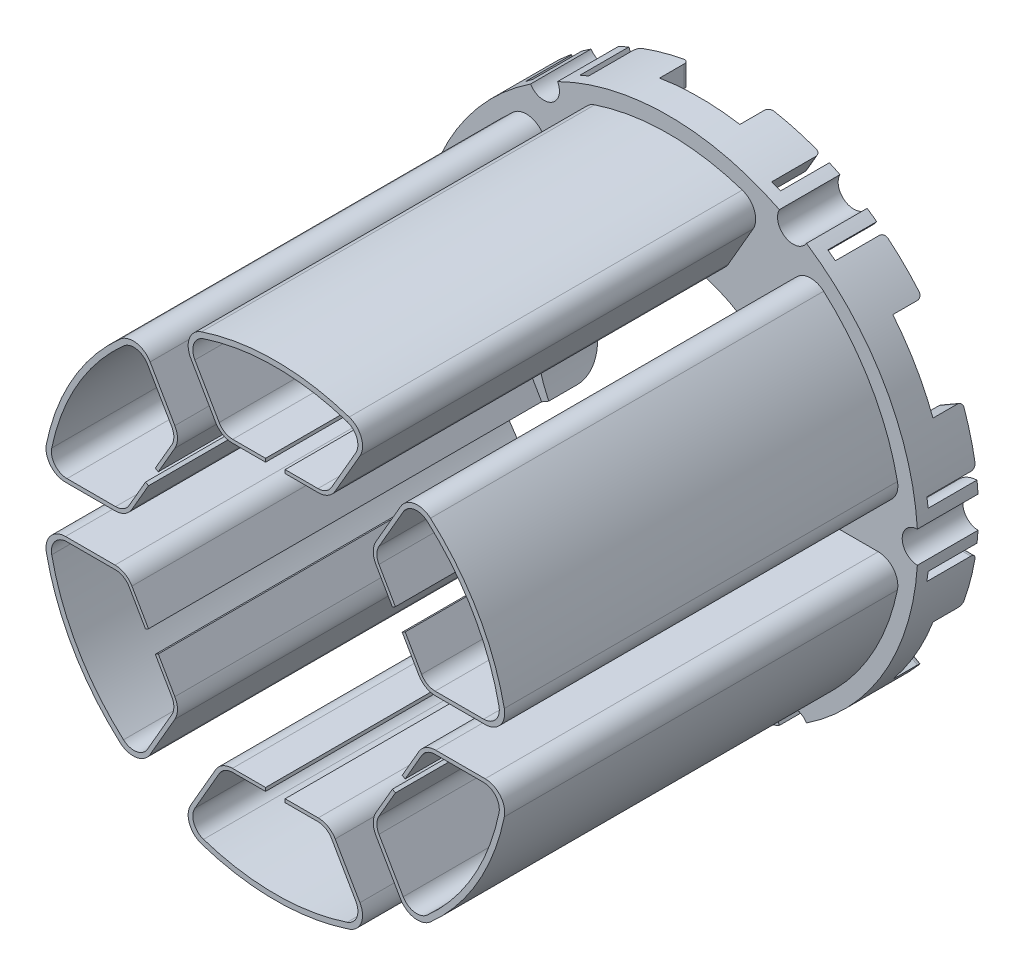
SolidWorks part; units mm, degrees
ref_plane "Ön Düzlem" through (0, 0, 0) normal (0, 0, 1) x (1, 0, 0)
ref_plane "Üst Düzlem" through (0, 0, 0) normal (0, 1, 0) x (1, 0, 0)
ref_plane "Sağ Düzlem" through (0, 0, 0) normal (1, 0, 0) x (0, 0, -1)
sketch "Çizim1" plane through (0, 0, 0) normal (0, 0, 1) x (1, 0, 0)
  line L0 (-5.5426, 14.4) -> (5.5426, 14.4)
  line L1 (9.6995, 12) -> (15.242, 2.4)
  line L2 (15.242, -2.4) -> (9.6995, -12)
  line L3 (5.5426, -14.4) -> (-5.5426, -14.4)
  line L4 (-9.6995, -12) -> (-15.242, -2.4)
  line L5 (-15.242, 2.4) -> (-9.6995, 12)
  line L7 (15.242, 2.4) -> (23.7792, 2.4)
  line L9 (9.6995, 12) -> (13.9681, 19.3934)
  line L10 (9.6995, -12) -> (13.9681, -19.3934)
  line L12 (-5.5426, 14.4) -> (-9.8111, 21.7934)
  line L13 (5.5426, 14.4) -> (9.8111, 21.7934)
  line L14 (15.242, -2.4) -> (23.7792, -2.4)
  line L15 (-5.5426, -14.4) -> (-9.8111, -21.7934)
  line L17 (5.5426, -14.4) -> (9.8111, -21.7934)
  line L18 (-15.242, -2.4) -> (-23.7792, -2.4)
  line L20 (-9.6995, -12) -> (-13.9681, -19.3934)
  line L21 (-9.6995, 12) -> (-13.9681, 19.3934)
  line L23 (-15.242, 2.4) -> (-23.7792, 2.4)
  arc A0 (-23.7792, -2.4) -> (-13.9681, -19.3934) centre (0, 0) ccw
  arc A1 (-13.9681, 19.3934) -> (-23.7792, 2.4) centre (0, 0) ccw
  arc A2 (9.8111, 21.7934) -> (-9.8111, 21.7934) centre (0, 0) ccw
  arc A3 (23.7792, 2.4) -> (13.9681, 19.3934) centre (0, 0) ccw
  arc A4 (13.9681, -19.3934) -> (23.7792, -2.4) centre (0, 0) ccw
  arc A5 (-9.8111, -21.7934) -> (9.8111, -21.7934) centre (0, 0) ccw
  point P6 (0, 14.4)
  point P18 (0, 0)
  point P32 (0, 0)
  point P43 (0, 0)
  dimension "D1" = 47.8
  dimension "D2" = 6
  dimension "D3" = 4.8
  dimension "D4" = 28.8
  dimension "D5" = 120
  dimension "D7" = 120
  dimension "D6" = 6
extrude "Yükseklik-Ekstrüzyon1" add sketch "Çizim1" along normal blind 40.2
sketch "Çizim2" plane through (0, 0, 0) normal (0, 0, -1) x (-1, 0, 0)
  circle A0 centre (0, 0) radius 25.5
  circle A1 centre (0, 0) radius 13.6
  dimension "D1" = 51
  dimension "D2" = 27.2
extrude "Yükseklik-Ekstrüzyon2" add sketch "Çizim2" along normal blind 1.2
sketch "Çizim3" plane through (0, 0, 40.2) normal (0, 0, 1) x (1, 0, 0)
  line L36 (-10.5944, 12.75) -> (-13.075, 17.0466)
  line L37 (-21.3003, 2.8) -> (-16.339, 2.8)
  line L38 (-14.9534, 3.6) -> (-10.5944, 11.15)
  line L39 (4.359, -14.75) -> (-4.359, -14.75)
  line L40 (-5.7446, -15.55) -> (-8.2253, -19.8466)
  line L41 (8.2253, -19.8466) -> (5.7446, -15.55)
  line L42 (-16.339, -2.8) -> (-21.3003, -2.8)
  line L43 (-13.075, -17.0466) -> (-10.5944, -12.75)
  line L44 (-10.5944, -11.15) -> (-14.9534, -3.6)
  line L45 (21.3003, -2.8) -> (16.339, -2.8)
  line L46 (14.9534, -3.6) -> (10.5944, -11.15)
  line L47 (10.5944, -12.75) -> (13.075, -17.0466)
  line L48 (13.075, 17.0466) -> (10.5944, 12.75)
  line L49 (10.5944, 11.15) -> (14.9534, 3.6)
  line L50 (16.339, 2.8) -> (21.3003, 2.8)
  line L51 (5.7446, 15.55) -> (8.2253, 19.8466)
  line L52 (-8.2253, 19.8466) -> (-5.7446, 15.55)
  line L53 (-4.359, 14.75) -> (4.359, 14.75)
  arc A60 (-13.075, 17.0466) -> (-15.5244, 17.4417) centre (-14.4607, 16.2466) ccw
  arc A61 (-15.5244, 17.4417) -> (-22.8672, 4.7237) centre (0, 0) ccw
  arc A62 (-22.8672, 4.7237) -> (-21.3003, 2.8) centre (-21.3003, 4.4) ccw
  arc A63 (-16.339, 2.8) -> (-14.9534, 3.6) centre (-16.339, 4.4) ccw
  arc A64 (-10.5944, 11.15) -> (-10.5944, 12.75) centre (-11.98, 11.95) ccw
  arc A65 (-4.359, -14.75) -> (-5.7446, -15.55) centre (-4.359, -16.35) ccw
  arc A66 (-8.2253, -19.8466) -> (-7.3428, -22.1654) centre (-6.8396, -20.6466) ccw
  arc A67 (-7.3428, -22.1654) -> (7.3428, -22.1654) centre (0, 0) ccw
  arc A68 (7.3428, -22.1654) -> (8.2253, -19.8466) centre (6.8396, -20.6466) ccw
  arc A69 (5.7446, -15.55) -> (4.359, -14.75) centre (4.359, -16.35) ccw
  arc A70 (-21.3003, -2.8) -> (-22.8672, -4.7237) centre (-21.3003, -4.4) ccw
  arc A71 (-22.8672, -4.7237) -> (-15.5244, -17.4417) centre (0, 0) ccw
  arc A72 (-15.5244, -17.4417) -> (-13.075, -17.0466) centre (-14.4607, -16.2466) ccw
  arc A73 (-10.5944, -12.75) -> (-10.5944, -11.15) centre (-11.98, -11.95) ccw
  arc A74 (-14.9534, -3.6) -> (-16.339, -2.8) centre (-16.339, -4.4) ccw
  arc A75 (16.339, -2.8) -> (14.9534, -3.6) centre (16.339, -4.4) ccw
  arc A76 (10.5944, -11.15) -> (10.5944, -12.75) centre (11.98, -11.95) ccw
  arc A77 (13.075, -17.0466) -> (15.5244, -17.4417) centre (14.4607, -16.2466) ccw
  arc A78 (15.5244, -17.4417) -> (22.8672, -4.7237) centre (0, 0) ccw
  arc A79 (22.8672, -4.7237) -> (21.3003, -2.8) centre (21.3003, -4.4) ccw
  arc A80 (22.8672, 4.7237) -> (15.5244, 17.4417) centre (0, 0) ccw
  arc A81 (15.5244, 17.4417) -> (13.075, 17.0466) centre (14.4607, 16.2466) ccw
  arc A82 (10.5944, 12.75) -> (10.5944, 11.15) centre (11.98, 11.95) ccw
  arc A83 (14.9534, 3.6) -> (16.339, 2.8) centre (16.339, 4.4) ccw
  arc A84 (21.3003, 2.8) -> (22.8672, 4.7237) centre (21.3003, 4.4) ccw
  arc A85 (8.2253, 19.8466) -> (7.3428, 22.1654) centre (6.8396, 20.6466) ccw
  arc A86 (7.3428, 22.1654) -> (-7.3428, 22.1654) centre (0, 0) ccw
  arc A87 (-7.3428, 22.1654) -> (-8.2253, 19.8466) centre (-6.8396, 20.6466) ccw
  arc A88 (-5.7446, 15.55) -> (-4.359, 14.75) centre (-4.359, 16.35) ccw
  arc A89 (4.359, 14.75) -> (5.7446, 15.55) centre (4.359, 16.35) ccw
extrude "Kes-Ekstrüzyon1" cut sketch "Çizim3" against normal up to surface (41.4 mm away) up to face at (-25.5, 0, -1.2)
sketch "Çizim4" plane through (0, 0, 40.2) normal (0, 0, 1) x (1, 0, 0)
  line L0 (-4.359, 14.75) -> (4.359, 14.75) construction
  line L1 (-1, 12.25) -> (1, 12.25)
  line L2 (-1, 12.25) -> (-1, 14.75)
  line L3 (-1, 14.75) -> (1, 14.75)
  line L4 (1, 12.25) -> (1, 14.75)
  line L5 (-1, 12.25) -> (1, 14.75) construction
  line L6 (-1, 14.75) -> (1, 12.25) construction
  line L7 (10.1088, 6.991) -> (12.2739, 8.241)
  line L8 (10.1088, 6.991) -> (11.1088, 5.259)
  line L9 (11.1088, 5.259) -> (13.2739, 6.509)
  line L10 (12.2739, 8.241) -> (13.2739, 6.509)
  line L11 (11.1088, -5.259) -> (13.2739, -6.509)
  line L12 (11.1088, -5.259) -> (10.1088, -6.991)
  line L13 (10.1088, -6.991) -> (12.2739, -8.241)
  line L14 (13.2739, -6.509) -> (12.2739, -8.241)
  line L15 (1, -12.25) -> (1, -14.75)
  line L16 (1, -12.25) -> (-1, -12.25)
  line L17 (-1, -12.25) -> (-1, -14.75)
  line L18 (1, -14.75) -> (-1, -14.75)
  line L19 (-10.1088, -6.991) -> (-12.2739, -8.241)
  line L20 (-10.1088, -6.991) -> (-11.1088, -5.259)
  line L21 (-11.1088, -5.259) -> (-13.2739, -6.509)
  line L22 (-12.2739, -8.241) -> (-13.2739, -6.509)
  line L23 (-11.1088, 5.259) -> (-13.2739, 6.509)
  line L24 (-11.1088, 5.259) -> (-10.1088, 6.991)
  line L25 (-10.1088, 6.991) -> (-12.2739, 8.241)
  line L26 (-13.2739, 6.509) -> (-12.2739, 8.241)
  point P0 (0, 13.5)
  point P30 (0, 0)
  dimension "D1" = 2
  dimension "D2" = 2.5
  dimension "D3" = 6
extrude "Kes-Ekstrüzyon2" cut sketch "Çizim4" against normal up to surface (41.4 mm away) up to face at (0, -18.2321, -1.2)
fillet "Radyus1" radius 2 24 edges at (13.9681, -19.3934, 20.1) (9.6995, -12, 20.1) (9.6995, 12, 20.1) (15.242, 2.4, 20.1) (23.7792, 2.4, 20.1) (15.242, -2.4, 20.1) (23.7792, -2.4, 20.1) (-15.242, -2.4, 20.1) (-9.6995, -12, 20.1) (-5.5426, 14.4, 20.1) (5.5426, -14.4, 20.1) (-5.5426, -14.4, 20.1) (9.8111, -21.7934, 20.1) (-9.8111, -21.7934, 20.1) (-13.9681, -19.3934, 20.1) (-23.7792, -2.4, 20.1) (-9.6995, 12, 20.1) (5.5426, 14.4, 20.1) (13.9681, 19.3934, 20.1) (9.8111, 21.7934, 20.1) (-9.8111, 21.7934, 20.1) (-13.9681, 19.3934, 20.1) (-15.242, 2.4, 20.1) (-23.7792, 2.4, 20.1)
sketch "Çizim7" plane through (0, 0, -1.2) normal (0, 0, -1) x (-1, 0, 0)
  line L0 (8.2759, 21.8342) -> (9.3638, 23.7185)
  line L1 (14.771, 18.0842) -> (15.859, 19.9685)
  line L2 (23.0469, 3.75) -> (25.2228, 3.75)
  line L3 (8.2253, 19.8466) -> (5.7446, 15.55) construction
  line L4 (23.0469, -3.75) -> (25.2228, -3.75)
  line L5 (8.8198, 22.7764) -> (15.315, 19.0264) construction
  line L6 (6.985, 17.6983) -> (11.8347, 14.8983) construction
  line L7 (10.5944, 12.75) -> (13.075, 17.0466) construction
  line L8 (24.1348, 3.75) -> (24.1348, -3.75) construction
  line L9 (18.8197, 2.8) -> (18.8197, -2.8) construction
  line L10 (14.771, -18.0842) -> (15.859, -19.9685)
  line L11 (8.2759, -21.8342) -> (9.3638, -23.7185)
  line L12 (15.315, -19.0264) -> (8.8198, -22.7764) construction
  line L13 (11.8347, -14.8983) -> (6.985, -17.6983) construction
  line L14 (-8.2759, -21.8342) -> (-9.3638, -23.7185)
  line L15 (-14.771, -18.0842) -> (-15.859, -19.9685)
  line L16 (-8.8198, -22.7764) -> (-15.315, -19.0264) construction
  line L17 (-6.985, -17.6983) -> (-11.8347, -14.8983) construction
  line L18 (-23.0469, -3.75) -> (-25.2228, -3.75)
  line L19 (-23.0469, 3.75) -> (-25.2228, 3.75)
  line L20 (-24.1348, -3.75) -> (-24.1348, 3.75) construction
  line L21 (-18.8197, -2.8) -> (-18.8197, 2.8) construction
  line L22 (-14.771, 18.0842) -> (-15.859, 19.9685)
  line L23 (-8.2759, 21.8342) -> (-9.3638, 23.7185)
  line L24 (-15.315, 19.0264) -> (-8.8198, 22.7764) construction
  line L25 (-11.8347, 14.8983) -> (-6.985, 17.6983) construction
  arc A0 (8.2759, 21.8342) -> (-8.2759, 21.8342) centre (0, 0) ccw
  arc A1 (9.3638, 23.7185) -> (-9.3638, 23.7185) centre (0, 0) ccw
  arc A2 (-14.771, 18.0842) -> (-23.0469, 3.75) centre (0, 0) ccw
  circle A3 centre (0, 0) radius 25.5
  arc A4 (-15.859, 19.9685) -> (-25.2228, 3.75) centre (0, 0) ccw
  arc A5 (23.0469, 3.75) -> (14.771, 18.0842) centre (0, 0) ccw
  arc A6 (25.2228, 3.75) -> (15.859, 19.9685) centre (0, 0) ccw
  arc A7 (14.771, -18.0842) -> (23.0469, -3.75) centre (0, 0) ccw
  arc A8 (15.859, -19.9685) -> (25.2228, -3.75) centre (0, 0) ccw
  arc A9 (-9.3638, -23.7185) -> (9.3638, -23.7185) centre (0, 0) ccw
  arc A10 (-8.2759, -21.8342) -> (8.2759, -21.8342) centre (0, 0) ccw
  arc A11 (-23.0469, -3.75) -> (-14.771, -18.0842) centre (0, 0) ccw
  arc A12 (-25.2228, -3.75) -> (-15.859, -19.9685) centre (0, 0) ccw
  point P17 (0, 0)
  point P60 (0, 0)
  dimension "D2" = 46.7
  dimension "D1" = 0
  dimension "D3" = 7.5
  dimension "D4" = 6
extrude "Yükseklik-Ekstrüzyon3" add sketch "Çizim7" along normal blind 5
sketch "Çizim8" plane through (0, 0, -6.2) normal (0, 0, -1) x (-1, 0, 0)
  line L0 (4.1083, 25.1669) -> (4.0972, 22.9877)
  line L1 (-4.1028, 25.1678) -> (-4.1028, 22.9867)
  line L3 (-1, 13.5632) -> (-1, 14.75) construction
  line L4 (4.1028, 24.0773) -> (-4.1028, 24.0773) construction
  line L5 (-3.693, 0) -> (3.693, 0) construction
  line L30 (23.8493, 9.0256) -> (21.9566, 7.9455)
  line L31 (19.7446, 16.137) -> (17.8557, 15.0465)
  line L32 (19.741, -16.1413) -> (17.8593, -15.0422)
  line L33 (23.8473, -9.0308) -> (21.9585, -7.9403)
  line L34 (-4.1083, -25.1669) -> (-4.0972, -22.9877)
  line L35 (4.1028, -25.1678) -> (4.1028, -22.9867)
  line L36 (-23.8493, -9.0256) -> (-21.9566, -7.9455)
  line L37 (-19.7446, -16.137) -> (-17.8557, -15.0465)
  line L38 (-19.741, 16.1413) -> (-17.8593, 15.0422)
  line L39 (-23.8473, 9.0308) -> (-21.9585, 7.9403)
  arc A0 (9.3638, 23.7185) -> (-9.3638, 23.7185) centre (0, 0) ccw construction
  arc A1 (8.2759, 21.8342) -> (-8.2759, 21.8342) centre (0, 0) ccw construction
  arc A2 (-23.0469, -3.75) -> (-14.771, -18.0842) centre (0, 0) ccw construction
  arc A3 (-25.2228, -3.75) -> (-15.859, -19.9685) centre (0, 0) ccw construction
  arc A4 (14.771, -18.0842) -> (23.0469, -3.75) centre (0, 0) ccw construction
  arc A5 (15.859, -19.9685) -> (25.2228, -3.75) centre (0, 0) ccw construction
  arc A6 (-8.2759, -21.8342) -> (8.2759, -21.8342) centre (0, 0) ccw construction
  arc A7 (-9.3638, -23.7185) -> (9.3638, -23.7185) centre (0, 0) ccw construction
  arc A8 (23.0469, 3.75) -> (14.771, 18.0842) centre (0, 0) ccw construction
  arc A9 (25.2228, 3.75) -> (15.859, 19.9685) centre (0, 0) ccw construction
  arc A10 (-14.771, 18.0842) -> (-23.0469, 3.75) centre (0, 0) ccw construction
  arc A11 (-15.859, 19.9685) -> (-25.2228, 3.75) centre (0, 0) ccw construction
  arc A12 (-21.9566, -7.9455) -> (-17.8557, -15.0465) centre (0, 0) ccw
  arc A13 (-23.8493, -9.0256) -> (-19.7446, -16.137) centre (0, 0) ccw
  arc A14 (17.8593, -15.0422) -> (21.9585, -7.9403) centre (0, 0) ccw
  arc A15 (19.741, -16.1413) -> (23.8473, -9.0308) centre (0, 0) ccw
  arc A16 (-4.0972, -22.9877) -> (4.1028, -22.9867) centre (0, 0) ccw
  arc A17 (-4.1083, -25.1669) -> (4.1028, -25.1678) centre (0, 0) ccw
  arc A18 (21.9566, 7.9455) -> (17.8557, 15.0465) centre (0, 0) ccw
  arc A19 (23.8493, 9.0256) -> (19.7446, 16.137) centre (0, 0) ccw
  arc A20 (4.0972, 22.9877) -> (-4.1028, 22.9867) centre (0, 0) ccw
  arc A21 (4.1083, 25.1669) -> (-4.1028, 25.1678) centre (0, 0) ccw
  arc A22 (-17.8593, 15.0422) -> (-21.9585, 7.9403) centre (0, 0) ccw
  arc A23 (-19.741, 16.1413) -> (-23.8473, 9.0308) centre (0, 0) ccw
  point P20 (0, 0)
  point P22 (0, 24.0773)
  point P73 (0, 0)
  dimension "D1" = 8.2111
  dimension "D2" = 8.2
  dimension "D3" = 6
extrude "Kes-Ekstrüzyon3" cut sketch "Çizim8" against normal blind 3
sketch "Çizim9" plane through (0, 0, -1.2) normal (0, 0, -1) x (-1, 0, 0)
  line L0 (-11.2461, -7.6476) -> (-12.2739, -8.241) construction
  line L1 (-12.2739, 8.241) -> (-11.2461, 7.6476) construction
  line L2 (-1, 13.5632) -> (-1, 14.75) construction
  line L3 (1, 14.75) -> (1, 13.5632) construction
  line L4 (-12.2461, 5.9156) -> (-13.2739, 6.509) construction
  line L5 (13.2739, 6.509) -> (12.2461, 5.9156) construction
  line L6 (11.2461, 7.6476) -> (12.2739, 8.241) construction
  line L7 (12.2461, -5.9156) -> (13.2739, -6.509) construction
  line L8 (-13.2739, -6.509) -> (-12.2461, -5.9156) construction
  line L9 (12.2739, -8.241) -> (11.2461, -7.6476) construction
  line L10 (1, -13.5632) -> (1, -14.75) construction
  line L11 (-1, -14.75) -> (-1, -13.5632) construction
  line L12 (12.2011, -8.199) -> (11.2461, -7.6476)
  line L13 (1, -13.5632) -> (1, -14.6659)
  line L14 (-1, -14.6659) -> (-1, -13.5632)
  line L15 (-11.2461, -7.6476) -> (-12.2011, -8.199)
  line L16 (-13.2011, -6.4669) -> (-12.2461, -5.9156)
  line L17 (12.2461, -5.9156) -> (13.2011, -6.4669)
  line L18 (11.2461, 7.6476) -> (12.2011, 8.199)
  line L19 (13.2011, 6.4669) -> (12.2461, 5.9156)
  line L20 (-12.2461, 5.9156) -> (-13.2011, 6.4669)
  line L21 (1, 14.6659) -> (1, 13.5632)
  line L22 (-1, 13.5632) -> (-1, 14.6659)
  line L23 (-12.2011, 8.199) -> (-11.2461, 7.6476)
  arc A0 (-1, 13.5632) -> (-11.2461, 7.6476) centre (0, 0) ccw construction
  arc A1 (11.2461, 7.6476) -> (1, 13.5632) centre (0, 0) ccw construction
  arc A2 (-12.2461, 5.9156) -> (-12.2461, -5.9156) centre (0, 0) ccw construction
  arc A3 (12.2461, -5.9156) -> (12.2461, 5.9156) centre (0, 0) ccw construction
  arc A4 (1, -13.5632) -> (11.2461, -7.6476) centre (0, 0) ccw construction
  arc A5 (-11.2461, -7.6476) -> (-1, -13.5632) centre (0, 0) ccw construction
  arc A6 (1, -13.5632) -> (11.2461, -7.6476) centre (0, 0) ccw
  arc A7 (-11.2461, -7.6476) -> (-1, -13.5632) centre (0, 0) ccw
  arc A8 (12.2461, -5.9156) -> (12.2461, 5.9156) centre (0, 0) ccw
  arc A9 (-12.2461, 5.9156) -> (-12.2461, -5.9156) centre (0, 0) ccw
  arc A10 (11.2461, 7.6476) -> (1, 13.5632) centre (0, 0) ccw
  arc A11 (-1, 13.5632) -> (-11.2461, 7.6476) centre (0, 0) ccw
  arc A12 (-1, 14.6659) -> (-12.2011, 8.199) centre (0, 0) ccw
  arc A13 (-13.2011, 6.4669) -> (-13.2011, -6.4669) centre (0, 0) ccw
  arc A14 (-12.2011, -8.199) -> (-1, -14.6659) centre (0, 0) ccw
  arc A15 (1, -14.6659) -> (12.2011, -8.199) centre (0, 0) ccw
  arc A16 (13.2011, -6.4669) -> (13.2011, 6.4669) centre (0, 0) ccw
  arc A17 (12.2011, 8.199) -> (1, 14.6659) centre (0, 0) ccw
  dimension "D1" = 29.4
extrude "Yükseklik-Ekstrüzyon4" add sketch "Çizim9" along normal blind 4.7
fillet "Radyus3" radius 3 12 edges at (-12.7236, 6.1913, -5.9) (-11.7236, 7.9233, -5.9) (-12.7236, -6.1913, -5.9) (-11.7236, -7.9233, -5.9) (-1, -14.1146, -5.9) (1, -14.1146, -5.9) (11.7236, -7.9233, -5.9) (12.7236, -6.1913, -5.9) (12.7236, 6.1913, -5.9) (-1, 14.1146, -5.9) (1, 14.1146, -5.9) (11.7236, 7.9233, -5.9)
sketch "Çizim10" plane through (0, 0, -1.2) normal (0, 0, 1) x (1, 0, 0)
  line L0 (-11.541, 15.1896) -> (-7.3841, 17.5896) construction
  line L1 (-10.2768, 13) -> (-12.8052, 17.3792) construction
  line L2 (-8.6483, 19.7792) -> (-6.1199, 15.4) construction
  line L3 (-9.4625, 16.3896) -> (-16.0375, 27.7777) construction
  circle A0 centre (0, 0) radius 25.5 construction
  arc A1 (-14.1099, 21.2406) -> (-11.3399, 22.8398) centre (-12.75, 22.0836) ccw
  arc A2 (-15.0944, 20.5526) -> (-10.2519, 23.3484) centre (-12.75, 22.0836) ccw
  arc A3 (-14.1099, 21.2406) -> (-15.0944, 20.5526) centre (0, 0) ccw
  circle A4 centre (-12.75, 22.0836) radius 2.8 construction
  circle A5 centre (-12.75, 22.0836) radius 1.6 construction
  arc A6 (-10.2519, 23.3484) -> (-11.3399, 22.8398) centre (0, 0) ccw
  arc A7 (11.3399, 22.8398) -> (10.2519, 23.3484) centre (0, 0) ccw
  arc A8 (10.2519, 23.3484) -> (15.0944, 20.5526) centre (12.75, 22.0836) ccw
  arc A9 (11.3399, 22.8398) -> (14.1099, 21.2406) centre (12.75, 22.0836) ccw
  arc A10 (15.0944, 20.5526) -> (14.1099, 21.2406) centre (0, 0) ccw
  arc A11 (25.4498, 1.5992) -> (25.3463, 2.7958) centre (0, 0) ccw
  arc A12 (25.3463, 2.7958) -> (25.3463, -2.7958) centre (25.5, 0) ccw
  arc A13 (25.4498, 1.5992) -> (25.4498, -1.5992) centre (25.5, 0) ccw
  arc A14 (25.3463, -2.7958) -> (25.4498, -1.5992) centre (0, 0) ccw
  arc A15 (14.1099, -21.2406) -> (15.0944, -20.5526) centre (0, 0) ccw
  arc A16 (15.0944, -20.5526) -> (10.2519, -23.3484) centre (12.75, -22.0836) ccw
  arc A17 (14.1099, -21.2406) -> (11.3399, -22.8398) centre (12.75, -22.0836) ccw
  arc A18 (10.2519, -23.3484) -> (11.3399, -22.8398) centre (0, 0) ccw
  arc A19 (-11.3399, -22.8398) -> (-10.2519, -23.3484) centre (0, 0) ccw
  arc A20 (-10.2519, -23.3484) -> (-15.0944, -20.5526) centre (-12.75, -22.0836) ccw
  arc A21 (-11.3399, -22.8398) -> (-14.1099, -21.2406) centre (-12.75, -22.0836) ccw
  arc A22 (-15.0944, -20.5526) -> (-14.1099, -21.2406) centre (0, 0) ccw
  arc A23 (-25.4498, -1.5992) -> (-25.3463, -2.7958) centre (0, 0) ccw
  arc A24 (-25.3463, -2.7958) -> (-25.3463, 2.7958) centre (-25.5, 0) ccw
  arc A25 (-25.4498, -1.5992) -> (-25.4498, 1.5992) centre (-25.5, 0) ccw
  arc A26 (-25.3463, 2.7958) -> (-25.4498, 1.5992) centre (0, 0) ccw
  point P50 (0, 0)
  dimension "D1" = 3.2
  dimension "D2" = 1.2
  dimension "D3" = 6
extrude "Yükseklik-Ekstrüzyon5" add sketch "Çizim10" against normal up to surface (5 mm away) up to face at (-17.1009, -17.353, -6.2)
sketch "Çizim11" plane through (0, 0, -1.2) normal (0, 0, -1) x (-1, 0, 0)
  arc A0 (-14.1099, 21.2406) -> (-11.3399, 22.8398) centre (-12.75, 22.0836) ccw construction
  arc A1 (-11.3399, 22.8398) -> (-14.1099, 21.2406) centre (0, 0) ccw construction
  arc A2 (11.3399, 22.8398) -> (14.1099, 21.2406) centre (12.75, 22.0836) ccw construction
  arc A3 (14.1099, 21.2406) -> (11.3399, 22.8398) centre (0, 0) ccw construction
  arc A4 (14.1099, -21.2406) -> (11.3399, -22.8398) centre (12.75, -22.0836) ccw construction
  arc A5 (11.3399, -22.8398) -> (14.1099, -21.2406) centre (0, 0) ccw construction
  arc A6 (-11.3399, -22.8398) -> (-14.1099, -21.2406) centre (-12.75, -22.0836) ccw construction
  arc A7 (-14.1099, -21.2406) -> (-11.3399, -22.8398) centre (0, 0) ccw construction
  arc A8 (25.4498, 1.5992) -> (25.4498, -1.5992) centre (25.5, 0) ccw construction
  arc A9 (25.4498, -1.5992) -> (25.4498, 1.5992) centre (0, 0) ccw construction
  arc A10 (-25.4498, -1.5992) -> (-25.4498, 1.5992) centre (-25.5, 0) ccw construction
  arc A11 (-25.4498, 1.5992) -> (-25.4498, -1.5992) centre (0, 0) ccw construction
  arc A12 (-14.1099, 21.2406) -> (-11.3399, 22.8398) centre (-12.75, 22.0836) ccw
  arc A13 (-11.3399, 22.8398) -> (-14.1099, 21.2406) centre (0, 0) ccw
  arc A14 (11.3399, 22.8398) -> (14.1099, 21.2406) centre (12.75, 22.0836) ccw
  arc A15 (14.1099, 21.2406) -> (11.3399, 22.8398) centre (0, 0) ccw
  arc A16 (14.1099, -21.2406) -> (11.3399, -22.8398) centre (12.75, -22.0836) ccw
  arc A17 (11.3399, -22.8398) -> (14.1099, -21.2406) centre (0, 0) ccw
  arc A18 (-11.3399, -22.8398) -> (-14.1099, -21.2406) centre (-12.75, -22.0836) ccw
  arc A19 (-14.1099, -21.2406) -> (-11.3399, -22.8398) centre (0, 0) ccw
  arc A20 (25.4498, 1.5992) -> (25.4498, -1.5992) centre (25.5, 0) ccw
  arc A21 (25.4498, -1.5992) -> (25.4498, 1.5992) centre (0, 0) ccw
  arc A22 (-25.4498, -1.5992) -> (-25.4498, 1.5992) centre (-25.5, 0) ccw
  arc A23 (-25.4498, 1.5992) -> (-25.4498, -1.5992) centre (0, 0) ccw
extrude "Kes-Ekstrüzyon4" cut sketch "Çizim11" against normal up to surface (1.2 mm away) up to face at (-25.5, 0, 0)
fillet "Radyus4" radius 0.5 24 edges at (-18.8001, 15.5917, -6.2) (-15.315, 19.0264, -6.2) (-22.9029, 8.4856, -6.2) (-24.1348, 3.75, -6.2) (-24.1348, -3.75, -6.2) (-22.9029, -8.4855, -6.2) (-15.315, -19.0264, -6.2) (-18.8002, -15.5917, -6.2) (-8.8198, -22.7764, -6.2) (-4.1028, -24.0773, -6.2) (4.1028, -24.0773, -6.2) (8.8198, -22.7764, -6.2) (15.315, -19.0264, -6.2) (18.8001, -15.5917, -6.2) (-8.8198, 22.7764, -6.2) (-4.1028, 24.0773, -6.2) (4.1028, 24.0773, -6.2) (8.8198, 22.7764, -6.2) (15.315, 19.0264, -6.2) (18.8002, 15.5917, -6.2) (22.9029, 8.4855, -6.2) (24.1348, 3.75, -6.2) (24.1348, -3.75, -6.2) (22.9029, -8.4856, -6.2)
